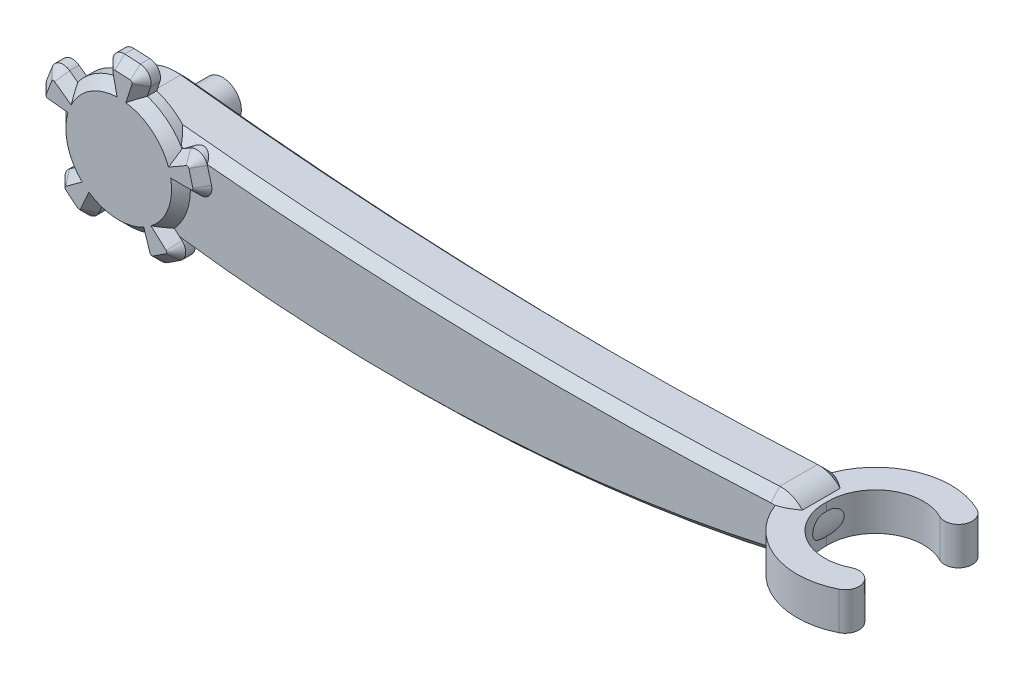
SolidWorks part; units mm, degrees
ref_plane "Front Plane" through (0, 0, 0) normal (0, 0, 1) x (1, 0, 0)
ref_plane "Top Plane" through (0, 0, 0) normal (0, 1, 0) x (1, 0, 0)
ref_plane "Right Plane" through (0, 0, 0) normal (1, 0, 0) x (0, 0, -1)
sketch "Sketch1" plane through (0, 0, 0) normal (0, 0, 1) x (1, 0, 0)
  line L0 (-85.28, 0) -> (85.28, 0)
  circle A0 centre (-85.28, 0) radius 12.6061
  circle A1 centre (85.28, 0) radius 7.5
  arc A2 (-83.8419, 12.5238) -> (84.8703, 7.4888) centre (30.238, 1005.9953) ccw
  arc A3 (-87.3583, -12.4336) -> (86.9487, -7.312) centre (-13.1707, 431.409) ccw
  point P4 (0, 0)
  dimension "D2" = 25.2121
  dimension "D1" = 15
sketch "Sketch3" plane through (0, 0, 0) normal (0, 0, 1) x (1, 0, 0)
extrude "Boss-Extrude2" add sketch "Sketch1" along normal mid plane 15 contours A2 A0 L0 A1 | A0 A3 A1 L0 | A0 | A1 region at (-5.4299, 3.948, 0) region at (-77.3644, -9.3485, 0) region at (-2.3505, -8.323, 0) region at (79.9878, 5.0106, 0)
chamfer "Chamfer1" distance 2.5 angle 45 8 edges at (92.7071, 1.043, -7.5) (0.4078, 6.4404, -7.5) (-97.7628, 1.7588, -7.5) (0.0457, -18.3969, -7.5) (-97.7628, 1.7588, 7.5) (0.4078, 6.4404, 7.5) (92.7071, 1.043, 7.5) (0.0457, -18.3969, 7.5)
sketch "Sketch4" plane through (0, 0, 7.5) normal (0, 0, 1) x (1, 0, 0)
  circle A0 centre (-85.28, 0) radius 16.5
  circle A1 centre (85.28, 0) radius 9.8495
  dimension "D1" = 33
extrude "Boss-Extrude3" add sketch "Sketch4" along normal mid plane 5 contours A0
sketch "Sketch5" plane through (0, 0, 10) normal (0, 0, 1) x (1, 0, 0)
  line L0 (-85.28, 0) -> (-66.0957, 0)
  line L1 (-63.1979, 3.7765) -> (-64.2681, 7.7705)
  line L2 (-68.6659, 9.5922) -> (-85.28, 0)
  line L3 (-85.28, 0) -> (-63.733, 5.7735) construction
  line L4 (-71.0233, -12.8368) -> (-85.28, 0)
  line L5 (-85.28, 0) -> (-79.3517, -18.2454)
  line L6 (-74.8646, -19.8343) -> (-71.3967, -17.5823)
  line L7 (-93.083, -17.5258) -> (-85.28, 0)
  line L8 (-85.28, 0) -> (-100.8005, -11.2763)
  line L9 (-100.9251, -16.0348) -> (-97.7116, -18.637)
  line L10 (-104.3592, 2.0053) -> (-85.28, 0)
  line L11 (-85.28, 0) -> (-100.8005, 11.2763)
  line L12 (-105.3646, 9.9243) -> (-106.8464, 6.064)
  line L13 (-89.2687, 18.7651) -> (-85.28, 0)
  line L14 (-85.28, 0) -> (-79.3517, 18.2454)
  line L15 (-82.0479, 22.1683) -> (-86.1772, 22.3847)
  arc A0 (-63.1979, 3.7765) -> (-66.0957, 0) centre (-66.0957, 3) cw
  arc A1 (-68.6659, 9.5922) -> (-64.2681, 7.7705) centre (-67.1659, 6.9941) cw
  arc A2 (-71.0233, -12.8368) -> (-71.3967, -17.5823) centre (-73.0307, -15.0663) cw
  arc A3 (-74.8646, -19.8343) -> (-79.3517, -18.2454) centre (-76.4985, -17.3183) cw
  arc A4 (-93.083, -17.5258) -> (-97.7116, -18.637) centre (-95.8236, -16.3056) cw
  arc A5 (-100.9251, -16.0348) -> (-100.8005, -11.2763) centre (-99.0371, -13.7033) cw
  arc A6 (-104.3592, 2.0053) -> (-106.8464, 6.064) centre (-104.0457, 4.9889) cw
  arc A7 (-105.3646, 9.9243) -> (-100.8005, 11.2763) centre (-102.5638, 8.8492) cw
  arc A8 (-89.2687, 18.7651) -> (-86.1772, 22.3847) centre (-86.3342, 19.3888) cw
  arc A9 (-82.0479, 22.1683) -> (-79.3517, 18.2454) centre (-82.2049, 19.1724) cw
  circle A10 centre (-85.28, 0) radius 2
  point P10 (-65.28, 11.547)
  dimension "D3" = 3
  dimension "D6" = 4
  dimension "D1" = 30
  dimension "D2" = 20
  dimension "D4" = 19.1843
  dimension "D5" = 5
extrude "Boss-Extrude4" add sketch "Sketch5" against normal blind 5 contours L14 A9 L15 A8 L13 | L2 L0 A0 L1 A1 | L5 A3 L6 A2 L4 | L8 A5 L9 A4 L7 | L11 A7 L12 A6 L10
chamfer "Chamfer2" distance 2.5 angle 45 30 edges at (-69.8282, 8.9211, 10) (-66.0178, 9.7657, 10) (-63.733, 5.7735, 10) (-63.7156, 1.1737, 10) (-67.4378, 0, 10) (-69.8759, -5.9131, 10) (-72.0207, -11.9387, 10) (-70.0399, -15.3016, 10) (-73.1307, -18.7083, 10) (-77.5, -20.1463, 10) (-79.7665, -16.9689, 10) (-86.1435, -16.4774, 10) (-92.5371, -16.2996, 10) (-95.1233, -19.2227, 10) (-99.3183, -17.3359, 10) (-102.0361, -13.6248, 10) (-99.7146, -10.4874, 10) (-101.2178, -4.2705, 10) (-103.0244, 1.865, 10) (-106.6036, 3.4214, 10) (-106.1055, 7.9942, 10) (-103.4159, 11.7257, 10) (-99.7146, 10.4874, 10) (-94.2665, 13.8381, 10) (-88.9896, 17.4523, 10) (-88.6154, 21.3372, 10) (-84.1125, 22.2765, 10) (-79.7325, 20.8717, 10) (-79.7665, 16.9689, 10) (-74.8962, 12.8229, 10)
sketch "Sketch7" plane through (0, 0, -7.5) normal (0, 0, -1) x (-1, 0, 0)
  circle A0 centre (85.28, 0) radius 5
  dimension "D1" = 10
extrude "Boss-Extrude5" add sketch "Sketch7" along normal blind 10
sketch "Sketch9" plane through (0, 0, 0) normal (0, 1, 0) x (1, 0, 0)
  line L0 (0, 0) -> (92.2128, 0) construction
  line L1 (84.8703, -5) -> (84.8703, 5) construction
  arc A0 (84.8703, 0) -> (113.8639, 18.2776) centre (104.8659, 0.416) cw
  arc A1 (92.2128, 0) -> (110.5616, 11.7224) centre (104.8659, 0.416) cw
  arc A2 (113.8639, 18.2776) -> (110.5616, 11.7224) centre (112.2128, 15) cw
  arc A3 (113.8639, -18.2776) -> (110.5616, -11.7224) centre (112.2128, -15) ccw
  arc A4 (92.2128, 0) -> (110.5616, -11.7224) centre (104.8659, -0.416) ccw
  arc A5 (84.8703, 0) -> (113.8639, -18.2776) centre (104.8659, -0.416) ccw
  dimension "D1" = 3.67
  dimension "D2" = 20
  dimension "D3" = 15
  dimension "D4" = 20
extrude "Boss-Extrude6" add sketch "Sketch9" along normal mid plane 10
